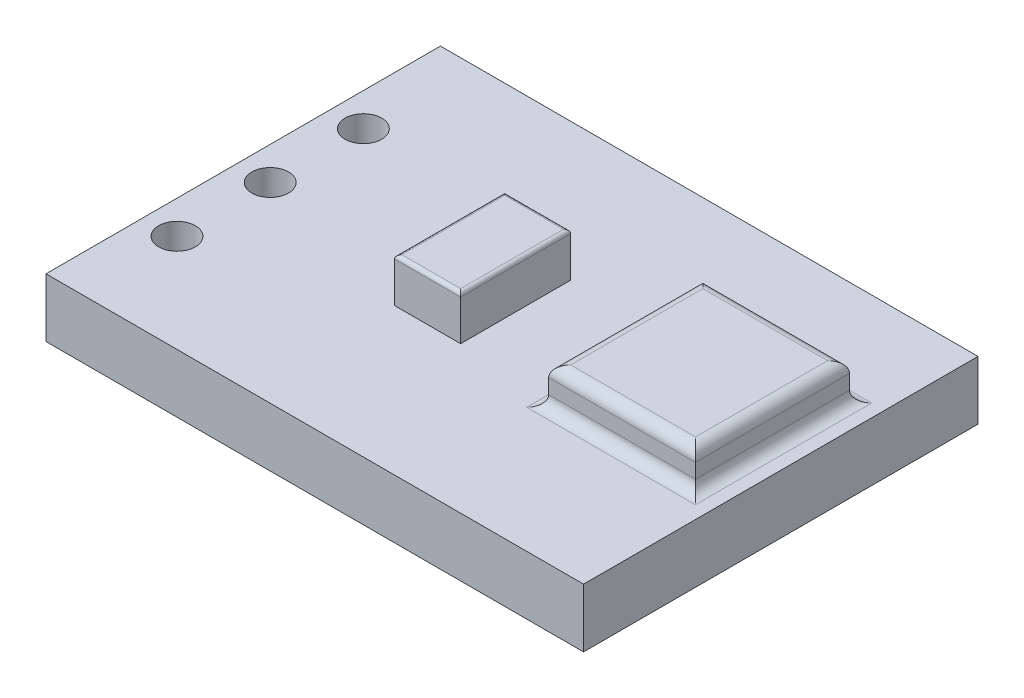
SolidWorks part; units mm, degrees
ref_plane "Front Plane" through (0, 0, 0) normal (0, 0, 1) x (1, 0, 0)
ref_plane "Top Plane" through (0, 0, 0) normal (0, 1, 0) x (1, 0, 0)
ref_plane "Right Plane" through (0, 0, 0) normal (1, 0, 0) x (0, 0, -1)
sketch "Sketch1" plane through (0, 0, 0) normal (0, 1, 0) x (1, 0, 0)
  line L1 (-354.4329, -11.9183) -> (-339.7829, -11.9183)
  line L2 (-354.4329, -11.9183) -> (-354.4329, -1.1683)
  line L3 (-354.4329, -1.1683) -> (-339.7829, -1.1683)
  line L4 (-339.7829, -11.9183) -> (-339.7829, -1.1683)
  dimension "D1" = 14.65
  dimension "D2" = 10.75
extrude "Mic Board" add sketch "Sketch1" along normal blind 1.6
sketch "Sketch2" plane through (0, 1.6, 0) normal (0, 1, 0) x (1, 0, 0)
  line L6 (-339.7829, -1.1683) -> (-354.4329, -1.1683) construction
  line L9 (-353.5329, -1.1683) -> (-353.5329, -4.1683) construction
  line L10 (-353.5329, -4.1683) -> (-354.4329, -4.1683) construction
  line L13 (-354.4329, -1.1683) -> (-354.4329, -11.9183) construction
  circle A0 centre (-353.5329, -4.1683) radius 0.5
  circle A1 centre (-353.5329, -6.7083) radius 0.5
  circle A2 centre (-353.5329, -9.2483) radius 0.5
  dimension "D1" = 3
  dimension "D4" = 1
  dimension "D2" = 3
  dimension "D3" = 0.9
extrude "Pins" cut sketch "Sketch2" against normal up to surface (1.6 mm away) contours A0 | A2 | A1 up to face at (-347.1079, 0, 6.5433)
sketch "mic Sketch" plane through (0, 1.6, 0) normal (0, 1, 0) x (1, 0, 0)
  line L0 (-342.4329, -4.0183) -> (-342.4329, -1.1683) construction
  line L1 (-344.4329, -4.0183) -> (-340.4329, -4.0183)
  line L2 (-344.4329, -4.0183) -> (-344.4329, -8.2183)
  line L3 (-344.4329, -8.2183) -> (-340.4329, -8.2183)
  line L4 (-340.4329, -4.0183) -> (-340.4329, -8.2183)
  line L5 (-339.7829, -1.1683) -> (-354.4329, -1.1683) construction
  line L6 (-340.4329, -6.1183) -> (-339.7829, -6.1183) construction
  line L7 (-339.7829, -11.9183) -> (-339.7829, -1.1683) construction
  dimension "D1" = 2.85
  dimension "D2" = 4
  dimension "D3" = 4.2
  dimension "D4" = 0.65
extrude "Microphone" add sketch "mic Sketch" along normal blind 1 contours L4 L3 L2 L1
sketch "Op Amp Sketch" plane through (0, 1.6, 0) normal (0, 1, 0) x (1, 0, 0)
  line L0 (-348.9329, -11.9183) -> (-348.9329, -7.9183) construction
  line L1 (-354.4329, -11.9183) -> (-339.7829, -11.9183) construction
  line L2 (-348.9329, -6.4183) -> (-354.4329, -6.4183) construction
  line L3 (-348.9329, -7.9183) -> (-347.1329, -7.9183)
  line L4 (-348.9329, -7.9183) -> (-348.9329, -4.9183)
  line L5 (-348.9329, -4.9183) -> (-347.1329, -4.9183)
  line L6 (-347.1329, -7.9183) -> (-347.1329, -4.9183)
  line L7 (-354.4329, -1.1683) -> (-354.4329, -11.9183) construction
  dimension "D1" = 3
  dimension "D2" = 1.8
  dimension "D3" = 4
  dimension "D4" = 5.5
extrude "Op Amp" add sketch "Op Amp Sketch" along normal blind 1.2
fillet "Mic Fillet" radius 0.3 8 edges at (-342.4329, 1.6, 4.0183) (-344.4329, 1.6, 6.1183) (-342.4329, 1.6, 8.2183) (-340.4329, 1.6, 6.1183) (-342.4329, 2.6, 4.0183) (-340.4329, 2.6, 6.1183) (-342.4329, 2.6, 8.2183) (-344.4329, 2.6, 6.1183)
fillet "Op Amp Fillet" radius 0.1 4 edges at (-348.0329, 2.8, 4.9183) (-347.1329, 2.8, 6.4183) (-348.0329, 2.8, 7.9183) (-348.9329, 2.8, 6.4183)
